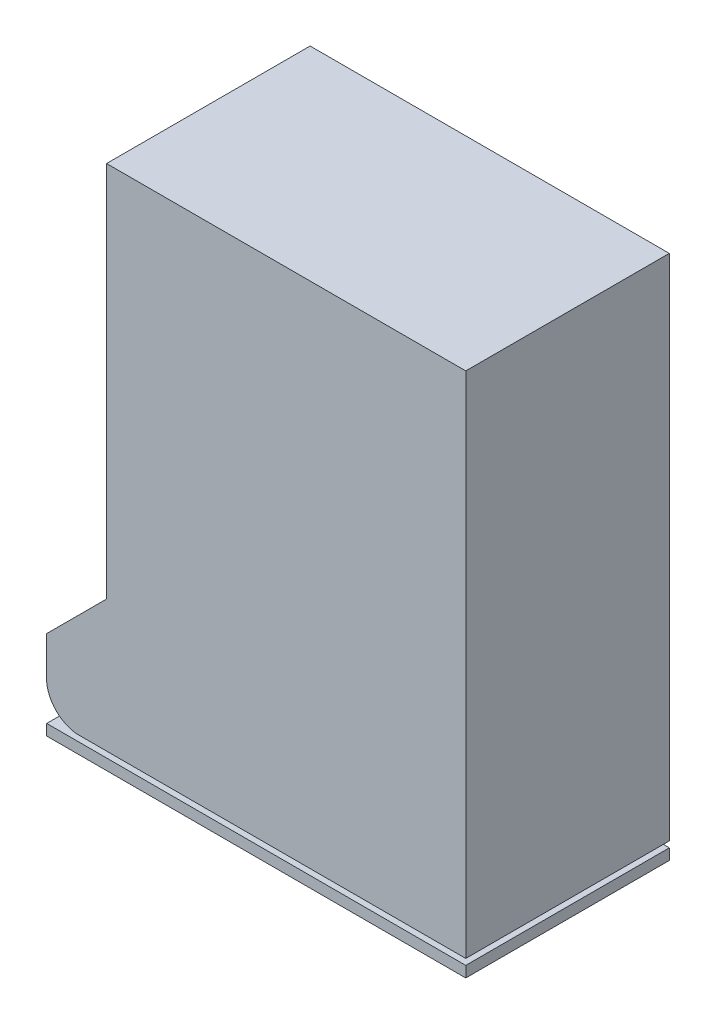
SolidWorks part; units mm, degrees
ref_plane "Front Plane" through (0, 0, 0) normal (0, 0, 1) x (1, 0, 0)
ref_plane "Top Plane" through (0, 0, 0) normal (0, 1, 0) x (1, 0, 0)
ref_plane "Right Plane" through (0, 0, 0) normal (1, 0, 0) x (0, 0, -1)
sketch "Sketch1" plane through (0, 0, 0) normal (0, 1, 0) x (1, 0, 0)
  line L1 (-28, -15) -> (28, -15)
  line L2 (-28, -15) -> (-28, 15)
  line L3 (-28, 15) -> (28, 15)
  line L4 (28, -15) -> (28, 15)
  line L5 (-28, -15) -> (28, 15) construction
  line L6 (-28, 15) -> (28, -15) construction
  point P0 (0, 0)
  dimension "D1" = 56
  dimension "D2" = 30
extrude "Boss-Extrude1" add sketch "Sketch1" along normal blind 2
sketch "Sketch2" plane through (0, 2, 0) normal (0, 1, 0) x (1, 0, 0)
  line L0 (-30, 17) -> (-30, -17)
  line L1 (-30, -17) -> (30, -17)
  line L2 (30, -17) -> (30, 17)
  line L3 (30, 17) -> (-30, 17)
  line L4 (28, -15) -> (28, 15)
  line L5 (28, 15) -> (-28, 15)
  line L6 (-28, 15) -> (-28, -15)
  line L7 (-28, -15) -> (28, -15)
  line L8 (28, -15) -> (28, 15)
  line L9 (28, 15) -> (-28, 15)
  line L10 (-28, 15) -> (-28, -15)
  line L11 (-28, -15) -> (28, -15)
  dimension "D1" = 0
  dimension "D2" = 2
extrude "Boss-Extrude2" add sketch "Sketch2" against normal blind 85
sketch "Sketch3" plane through (-30, 0, 0) normal (-1, 0, 0) x (0, 0, 1)
  line L0 (17, -83) -> (17, -73)
  line L1 (17, -83) -> (17, 2) construction
  line L2 (17, -73) -> (7.2997, -73)
  line L3 (-17, -83) -> (-17, 2) construction
  line L4 (-17, -73) -> (-17, -83)
  line L5 (-17, -83) -> (-10.0462, -76.0462)
  line L6 (-10.0462, -76.0462) -> (-7.2997, -73.2997)
  line L7 (17, -83) -> (7.2997, -73.2997)
  line L8 (7.2997, -73.2997) -> (7, -73)
  line L11 (-7.2997, -73) -> (-17, -73)
  line L12 (7, -73) -> (7.2997, -73)
  line L13 (-7.2997, -73.2997) -> (-7, -73)
  line L14 (-7, -73) -> (-7.2997, -73)
  dimension "D1" = 10
extrude "Boss-Extrude3" add sketch "Sketch3" along normal blind 10
sketch "Sketch5" plane through (-30, 0, 0) normal (-1, 0, 0) x (0, 0, 1)
  line L0 (-17, -73) -> (-17, 2) construction
  line L1 (17, -73) -> (-17, -73)
  line L2 (17, -73) -> (17, -71)
  line L3 (17, -71) -> (-17, -71)
  line L4 (-17, -73) -> (-17, -71)
  dimension "D1" = 2
extrude "Boss-Extrude5" add sketch "Sketch5" along normal blind 10
chamfer "Chamfer2" distance 10 angle 45 1 edges at (-30, -71, 0)
sketch "Sketch6" plane through (-30, 0, 0) normal (-1, 0, 0) x (0, 0, 1)
  line L4 (12.1716, -81) -> (14.1716, -83)
  line L5 (-17, -83) -> (17, -83) construction
  line L6 (-12.1716, -81) -> (-14.1716, -83)
  line L7 (-14.1716, -83) -> (14.1716, -83)
  line L8 (12.1716, -81) -> (6.1716, -75)
  line L9 (6.1716, -75) -> (-6.1716, -75)
  line L10 (-6.1716, -75) -> (-12.1716, -81)
  line L11 (-12.1716, -81) -> (12.1716, -81)
  line L12 (12.1716, -81) -> (6.1716, -75)
  line L13 (6.1716, -75) -> (-6.1716, -75)
  line L14 (-6.1716, -75) -> (-12.1716, -81)
  dimension "D1" = 2
extrude "Boss-Extrude6" add sketch "Sketch6" along normal up to surface (10 mm away) from offset 2 separate body up to face at (-40, -75.6667, 0)
sketch "Sketch7" plane through (0, 0, 17) normal (0, 0, 1) x (1, 0, 0)
  line L0 (-40, -83) -> (-40, -71) construction
  line L1 (-40, -83) -> (-30, -83) construction
  circle A0 centre (-36, -79) radius 2.25
  dimension "D3" = 4.5
  dimension "D1" = 4
  dimension "D2" = 4
extrude "Cut-Extrude1" cut sketch "Sketch7" against normal through all
sketch "Sketch9" plane through (0, 0, 17) normal (0, 0, 1) x (1, 0, 0)
  circle A0 centre (-36, -79) radius 2.25 construction
  circle A1 centre (-36, -79) radius 2.25
extrude "Boss-Extrude7" add sketch "Sketch9" against normal up to surface (4 mm away) up to face at (-36, -81.25, 15.25)
sketch "Sketch10" plane through (0, 0, -17) normal (0, 0, -1) x (-1, 0, 0)
  circle A0 centre (36, -79) radius 2.25 construction
  circle A1 centre (36, -79) radius 2.25
extrude "Boss-Extrude8" add sketch "Sketch10" against normal up to surface (4 mm away) up to face at (-36, -76.75, -10.75)
sketch "Sketch11" plane through (0, 0, 17) normal (0, 0, 1) x (1, 0, 0)
  line L0 (-40, -83) -> (-40, -71) construction
  line L1 (-40, -83) -> (-30, -83) construction
  circle A0 centre (-36, -79) radius 1.75
  point P6 (-33.4813, -71.2088)
  dimension "D3" = 3.5
  dimension "D1" = 4
  dimension "D2" = 4
extrude "Boss-Extrude9" add sketch "Sketch11" against normal up to surface (34 mm away) up to face at (-15.7143, -53.8571, -17)
sketch "Sketch12" plane through (0, -83, 0) normal (0, -1, 0) x (1, 0, 0)
  line L4 (-32, 14.1716) -> (-40, 14.1716)
  line L5 (-40, 14.1716) -> (-40, -14.1716)
  line L6 (-40, -14.1716) -> (-32, -14.1716)
  line L7 (-32, -14.1716) -> (-32, 14.1716)
  line L8 (-32, 14.1716) -> (-40, 14.1716)
  line L9 (-40, 14.1716) -> (-40, -14.1716)
  line L10 (-40, -14.1716) -> (-32, -14.1716)
  line L11 (-32, -14.1716) -> (-32, 14.1716)
  dimension "D1" = 0
extrude "Boss-Extrude10" add sketch "Sketch12" along normal blind 1
sketch "Sketch13" plane through (-40, 0, 0) normal (-1, 0, 0) x (0, 0, 1)
  line L0 (14.1716, -83) -> (15.1716, -84)
  line L1 (-14.1716, -83) -> (-15.1716, -84)
  line L2 (-14.1716, -84) -> (-14.1716, -83) construction
  line L3 (-17, -71) -> (-17, -83) construction
  line L4 (-14.1716, -83) -> (-6.1716, -75) construction
  line L5 (17, -85.8284) -> (-17, -85.8284)
  line L6 (15.1716, -84) -> (17, -84)
  line L7 (-17, -85.8284) -> (17, -85.8284)
  line L8 (-17, -85.8284) -> (-17, -84)
  line L9 (-17, -84) -> (-15.1716, -84)
  line L10 (17, -85.8284) -> (17, -84)
  line L11 (14.1716, -83) -> (-14.1716, -83)
  line M6 (-14.1716, -83) -> (-14.1716, -84)
  line M7 (-14.1716, -84) -> (14.1716, -84)
  line M8 (14.1716, -84) -> (14.1716, -83)
  dimension "D1" = 0
  dimension "D2" = 1
extrude "Boss-Extrude11" add sketch "Sketch13" against normal blind 8 contours L5 L10 L6 L0 L1 L9 L8 M8 M7 M6 region at (-40, -84.8945, 0)
sketch "Sketch14" plane through (-32, 0, 0) normal (1, 0, 0) x (0, 0, -1)
  line L1 (-17, -85.8284) -> (17, -85.8284)
  line L2 (-17, -85.8284) -> (-17, -84)
  line L3 (-17, -84) -> (17, -84)
  line L4 (17, -85.8284) -> (17, -84)
extrude "Boss-Extrude12" add sketch "Sketch14" along normal up to surface (62 mm away) up to face at (30, -40.5, 0)
fillet "Fillet1" radius 4 6 edges at (-40, -79.5, 10.6716) (-32, -79.5, 10.6716) (-32, -79.5, -10.6716) (-40, -79.5, -10.6716) (-40, -75, 0) (-32, -75, 0)
sketch "Sketch15" plane through (0, 0, 17) normal (0, 0, 1) x (1, 0, 0)
  line L0 (-40, -83) -> (-40, -71) construction
  line L1 (-40, -83) -> (-30, -83) construction
  line L2 (-40, -77) -> (-40.9583, -78.4292)
  line L3 (-40.9583, -78.4292) -> (-40.2216, -83.1921)
  line L4 (-40.2216, -83.1921) -> (-35, -83)
  arc A0 (-40, -77) -> (-35, -83) centre (-34.5, -77.5) ccw
extrude "Cut-Extrude2" cut sketch "Sketch15" against normal up to surface (6 mm away) up to face at (-36, -80.75, 14.75)
sketch "Sketch16" plane through (0, 0, -17) normal (0, 0, -1) x (-1, 0, 0)
  line L0 (40, -83) -> (30, -83) construction
  line L1 (40, -71) -> (40, -83) construction
  line L2 (40, -77) -> (40.9212, -77.9212)
  line L3 (40.9212, -77.9212) -> (40.1715, -83.2091)
  line L4 (40.1715, -83.2091) -> (35, -83)
  arc A0 (35, -83) -> (40, -77) centre (34.5, -77.5) ccw
extrude "Cut-Extrude3" cut sketch "Sketch16" against normal up to surface up to face at (-36, -77.25, -11.25)
